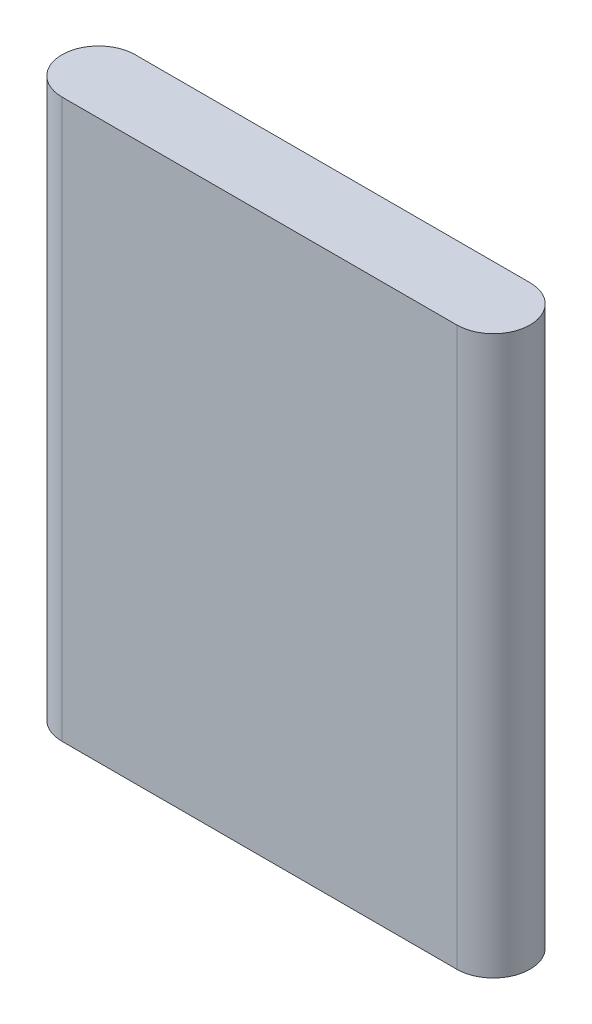
SolidWorks part; units mm, degrees
ref_plane "Front Plane" through (0, 0, 0) normal (0, 0, 1) x (1, 0, 0)
ref_plane "Top Plane" through (0, 0, 0) normal (0, 1, 0) x (1, 0, 0)
ref_plane "Right Plane" through (0, 0, 0) normal (1, 0, 0) x (0, 0, -1)
sketch "Sketch1" plane through (0, 0, 0) normal (0, 0, 1) x (1, 0, 0)
  line L1 (-25.25, 30.1) -> (25.25, 30.1)
  line L2 (-25.25, 30.1) -> (-25.25, -30.1)
  line L3 (-25.25, -30.1) -> (25.25, -30.1)
  line L4 (25.25, 30.1) -> (25.25, -30.1)
  line L5 (-25.25, 30.1) -> (25.25, -30.1) construction
  line L6 (-25.25, -30.1) -> (25.25, 30.1) construction
  point P0 (0, 0)
  dimension "D1" = 50.5
  dimension "D2" = 60.2
extrude "Boss-Extrude1" add sketch "Sketch1" along normal mid plane 7.9
fillet "Fillet1" 2 edges at (-25.25, 0, -3.95) (-25.25, 0, 3.95) type full round first side face at (0, 0, -3.95) second side face at (0, 0, 3.95) middle face at (-25.25, 0, 0)
fillet "Fillet2" 2 edges at (25.25, 0, 3.95) (25.25, 0, -3.95) type full round first side face at (1.975, 0, 3.95) second side face at (1.975, 0, -3.95) middle face at (25.25, 0, 0)
